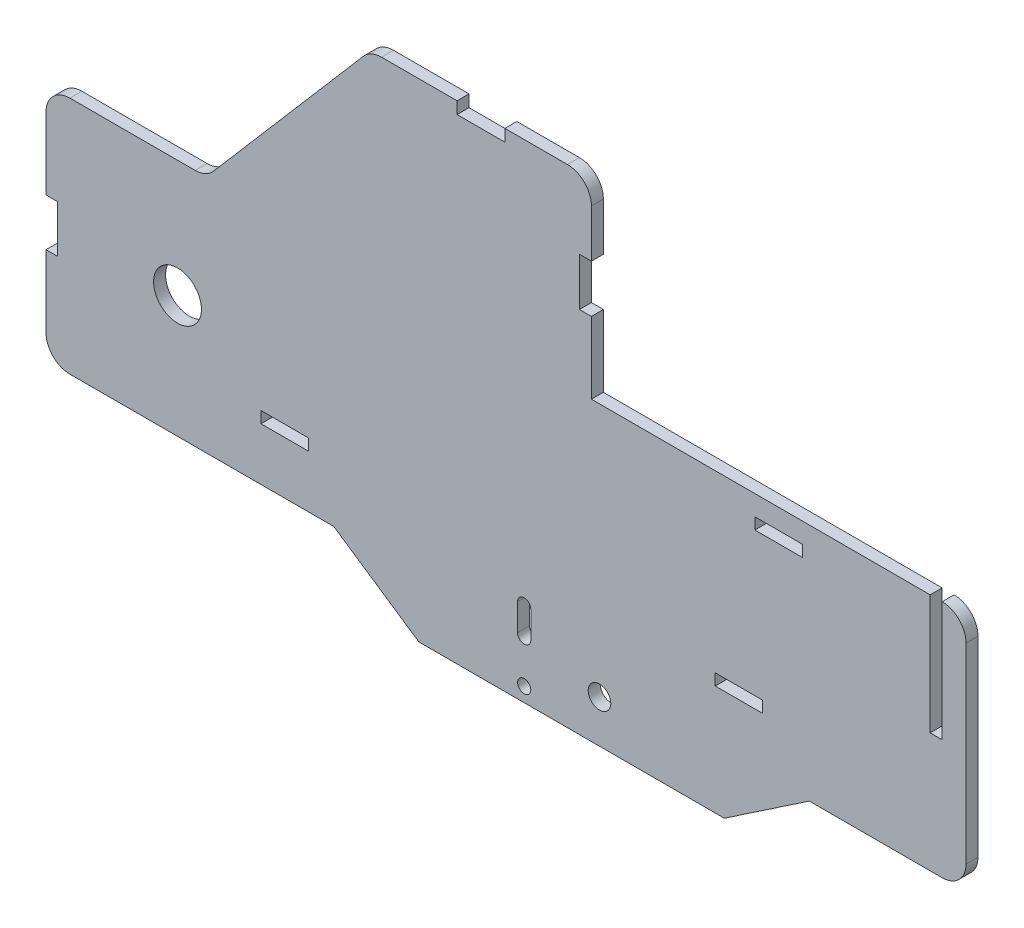
SolidWorks part; units mm, degrees
ref_plane "Front Plane" through (0, 0, 0) normal (0, 0, 1) x (1, 0, 0)
ref_plane "Top Plane" through (0, 0, 0) normal (0, 1, 0) x (1, 0, 0)
ref_plane "Right Plane" through (0, 0, 0) normal (1, 0, 0) x (0, 0, -1)
sketch "Sketch1" plane through (0, 0, 0) normal (0, 0, 1) x (1, 0, 0)
  line L0 (62.1239, 6.35) -> (131.9663, 6.35)
  line L1 (201.8088, 12.7) -> (201.8088, 76.2)
  line L2 (201.8088, 76.2) -> (102.3141, 76.2)
  line L3 (102.3141, 76.2) -> (102.3141, 127)
  line L4 (102.3141, 127) -> (43.6394, 127)
  line L5 (43.6394, 127) -> (0, 76.2)
  line L6 (0, 76.2) -> (-42.5392, 76.2)
  line L7 (-42.5392, 76.2) -> (-42.5392, 12.7)
  line L9 (-42.5392, 12.7) -> (46.6174, 12.7)
  line L10 (46.6174, 12.7) -> (62.1239, 6.35)
  line L11 (201.8088, 12.7) -> (147.4729, 12.7)
  line L12 (147.4729, 12.7) -> (131.9663, 6.35)
  dimension "D1" = 244.348
  dimension "D2" = 6.35
  dimension "D3" = 50.8
  dimension "D4" = 63.5
  dimension "D5" = 99.4947
  dimension "D6" = 16.7564
  dimension "D7" = 16.7564
extrude "Main Side" add sketch "Sketch1" along normal blind 3.175
sketch "Sketch2" plane through (0, 0, 3.175) normal (0, 0, 1) x (1, 0, 0)
  line L0 (-39.4912, 76.2) -> (-39.4912, 12.7) construction
  line L15 (0, 76.2) -> (-42.5392, 76.2) construction
  line L16 (-42.5392, 76.2) -> (-42.5392, 12.7) construction
  line L26 (-39.4912, 18.5744) -> (201.8088, 18.5744) construction
  line L27 (201.8088, 12.7) -> (201.8088, 76.2) construction
  line L28 (81.1588, 18.5744) -> (81.1588, 127) construction
  line L29 (102.3141, 127) -> (43.6394, 127) construction
  line L30 (81.1588, 36.7006) -> (201.8088, 36.7006) construction
  line L41 (62.1239, 6.35) -> (131.9663, 6.35) construction
  line L42 (135.1973, 29.718) -> (147.7703, 29.718)
  line L43 (135.1973, 29.718) -> (135.1973, 26.67)
  line L44 (135.1973, 26.67) -> (147.7703, 26.67)
  line L45 (147.7703, 29.718) -> (147.7703, 26.67)
  line L46 (14.5473, 29.718) -> (14.5473, 26.67)
  line L47 (27.1203, 26.67) -> (14.5473, 26.67)
  line L48 (27.1203, 29.718) -> (27.1203, 26.67)
  line L49 (27.1203, 29.718) -> (14.5473, 29.718)
  line L51 (-42.5392, 12.7) -> (46.6174, 12.7) construction
  point P20 (141.4838, 29.718)
  point P21 (141.4838, 36.7006)
  dimension "D1" = 12.573
  dimension "D2" = 3.048
  dimension "D3" = 20.32
  dimension "D4" = 3.048
extrude "Bottom Plate Holes" cut sketch "Sketch2" against normal through all
sketch "Sketch3" plane through (0, 0, 3.175) normal (0, 0, 1) x (1, 0, 0)
  line L1 (145.7115, 70.866) -> (158.4115, 70.866)
  line L2 (145.7115, 70.866) -> (145.7115, 67.818)
  line L3 (145.7115, 67.818) -> (158.4115, 67.818)
  line L4 (158.4115, 70.866) -> (158.4115, 67.818)
  line L6 (147.7703, 29.718) -> (135.1973, 29.718) construction
  line L7 (201.8088, 76.2) -> (102.3141, 76.2) construction
  point P8 (152.0615, 76.2)
  point P9 (152.0615, 70.866)
  dimension "D1" = 12.7
  dimension "D2" = 3.048
  dimension "D3" = 38.1
extrude "Cut-Extrude1" cut sketch "Sketch3" against normal through all
sketch "Sketch4" plane through (0, 0, 3.175) normal (0, 0, 1) x (1, 0, 0)
  line L0 (-42.5392, 76.2) -> (-42.5392, 12.7) construction
  line L1 (-42.5392, 50.7365) -> (-39.4912, 50.7365)
  line L2 (-42.5392, 50.7365) -> (-42.5392, 38.1635)
  line L3 (-42.5392, 38.1635) -> (-39.4912, 38.1635)
  line L4 (-39.4912, 50.7365) -> (-39.4912, 38.1635)
  point P6 (-42.5392, 44.45)
  point P7 (-42.5392, 44.45)
  dimension "D1" = 3.048
  dimension "D2" = 12.573
extrude "Cut-Extrude2" cut sketch "Sketch4" against normal through all
sketch "Sketch5" plane through (0, 0, 3.175) normal (0, 0, 1) x (1, 0, 0)
  line L0 (201.8088, 76.2) -> (102.3141, 76.2) construction
  line L1 (192.2838, 76.2) -> (195.4588, 76.2)
  line L2 (192.2838, 76.2) -> (192.2838, 44.45)
  line L3 (192.2838, 44.45) -> (195.4588, 44.45)
  line L4 (195.4588, 76.2) -> (195.4588, 44.45)
  line L5 (201.8088, 12.7) -> (201.8088, 76.2) construction
  dimension "D1" = 3.175
  dimension "D2" = 31.75
  dimension "D3" = 6.35
extrude "Cut-Extrude3" cut sketch "Sketch5" against normal through all
sketch "Sketch6" plane through (0, 0, 3.175) normal (0, 0, 1) x (1, 0, 0)
  line L0 (-42.5392, 76.2) -> (-42.5392, 50.7365) construction
  line L1 (0, 76.2) -> (-42.5392, 76.2) construction
  circle A0 centre (-7.6142, 45.085) radius 6.35
  dimension "D2" = 31.115
  dimension "D3" = 12.7
  dimension "D1" = 34.925
extrude "Cut-Extrude4" cut sketch "Sketch6" against normal through all
sketch "Sketch7" plane through (0, 0, 3.175) normal (0, 0, 1) x (1, 0, 0)
  line L0 (102.3141, 127) -> (43.6394, 127) construction
  line L1 (66.6267, 127) -> (79.3267, 127)
  line L2 (66.6267, 127) -> (66.6267, 123.825)
  line L3 (66.6267, 123.825) -> (79.3267, 123.825)
  line L4 (79.3267, 127) -> (79.3267, 123.825)
  point P6 (72.9767, 127)
  point P7 (72.9767, 127)
  dimension "D1" = 3.175
  dimension "D2" = 12.7
extrude "Cut-Extrude5" cut sketch "Sketch7" against normal through all
sketch "Sketch8" plane through (0, 0, 3.175) normal (0, 0, 1) x (1, 0, 0)
  line L0 (102.3141, 76.2) -> (102.3141, 127) construction
  line L1 (99.1391, 107.95) -> (102.3141, 107.95)
  line L2 (99.1391, 107.95) -> (99.1391, 95.25)
  line L3 (99.1391, 95.25) -> (102.3141, 95.25)
  line L4 (102.3141, 107.95) -> (102.3141, 95.25)
  point P6 (102.3141, 101.6)
  point P7 (102.3141, 101.6)
  dimension "D1" = 3.175
  dimension "D2" = 12.7
extrude "Cut-Extrude6" cut sketch "Sketch8" against normal through all
sketch "Sketch13" plane through (0, 0, 3.175) normal (0, 0, 1) x (1, 0, 0)
  line L1 (-42.5392, 12.7) -> (46.6174, 12.7) construction
  line L4 (147.4729, 12.7) -> (201.8088, 12.7) construction
  line L5 (33.9174, 12.7) -> (56.4826, -2.54)
  line L6 (56.4826, -2.54) -> (137.6077, -2.54)
  line L7 (137.6077, -2.54) -> (160.1729, 12.7)
  line L8 (33.9174, 12.7) -> (46.6174, 12.7)
  line L9 (46.6174, 12.7) -> (62.1239, 6.35)
  line L10 (62.1239, 6.35) -> (131.9663, 6.35)
  line L11 (131.9663, 6.35) -> (147.4729, 12.7)
  line L12 (147.4729, 12.7) -> (160.1729, 12.7)
  dimension "D1" = 8.89
  dimension "D2" = 12.7
  dimension "D3" = 12.7
  dimension "D4" = 145.966
  dimension "D5" = 145.966
extrude "Boss-Extrude2" add sketch "Sketch13" against normal blind 3.175
sketch "Sketch10" plane through (0, 0, 3.175) normal (0, 0, 1) x (1, 0, 0)
  line L0 (84.4608, 19.8624) -> (84.4608, 12.6776) construction
  line L1 (86.2108, 19.8624) -> (86.2108, 12.6776)
  line L2 (82.7108, 19.8624) -> (82.7108, 12.6776)
  line L3 (84.4608, 16.27) -> (84.4608, 1.27) construction
  line L4 (-42.5392, 38.1635) -> (-42.5392, 12.7) construction
  line L6 (56.4826, -2.54) -> (137.6077, -2.54) construction
  circle A0 centre (84.4608, 1.27) radius 1.75
  arc A1 (86.2108, 19.8624) -> (82.7108, 19.8624) centre (84.4608, 19.8624) ccw
  arc A2 (82.7108, 12.6776) -> (86.2108, 12.6776) centre (84.4608, 12.6776) ccw
  circle A3 centre (104.4608, 8.77) radius 3
  point P4 (84.4608, 16.27)
  point P11 (0, 0)
  point P13 (84.4608, 8.77)
  point P14 (0, 0)
  point P15 (111.7531, 17.3232)
  point P16 (0, 0)
  point P17 (91.963, 1.5816)
  point P20 (0, 0)
  point P21 (84.4608, 1.9275)
  dimension "D2" = 3.5
  dimension "D4" = 6
  dimension "D6" = 7.1848
  dimension "D1" = 15
  dimension "D3" = 3.5
  dimension "D5" = 20
  dimension "D7" = 127
  dimension "D8" = 3.81
extrude "Cut-Extrude7" cut sketch "Sketch10" against normal through all
fillet "Fillet1" radius 6.35 7 edges at (102.3141, 127, 1.5875) (43.6394, 127, 1.5875) (0, 76.2, 1.5875) (201.8088, 12.7, 1.5875) (-42.5392, 12.7, 1.5875) (201.8088, 76.2, 1.5875) (-42.5392, 76.2, 1.5875)
